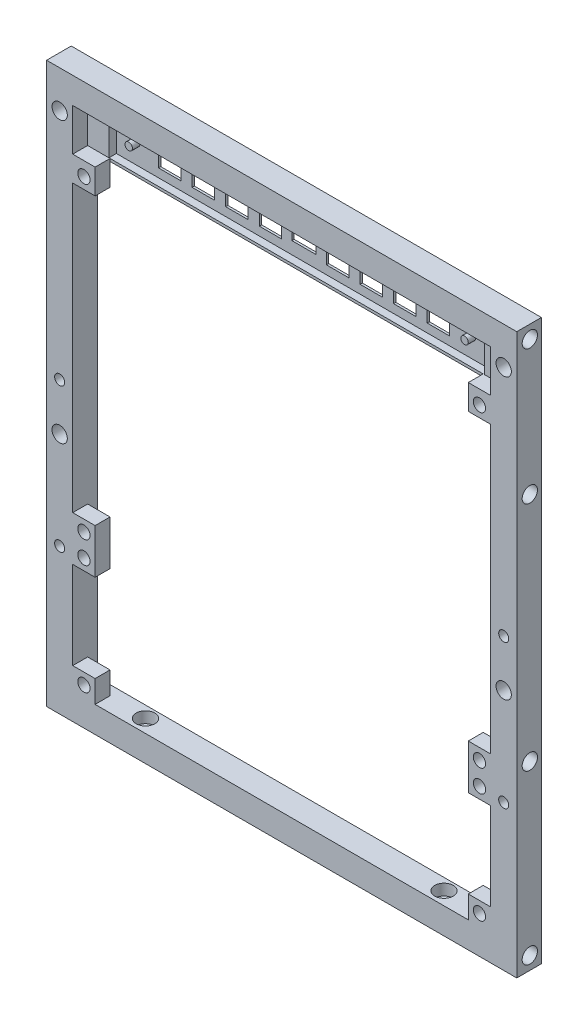
SolidWorks part; units mm, degrees
ref_plane "Front Plane" through (0, 0, 0) normal (0, 0, 1) x (1, 0, 0)
ref_plane "Top Plane" through (0, 0, 0) normal (0, 1, 0) x (1, 0, 0)
ref_plane "Right Plane" through (0, 0, 0) normal (1, 0, 0) x (0, 0, -1)
sketch "Sketch1" plane through (0, 0, 0) normal (0, 0, 1) x (1, 0, 0)
  line L1 (-63, -75) -> (63, -75)
  line L2 (-63, -75) -> (-63, 75)
  line L3 (-63, 75) -> (63, 75)
  line L4 (63, -75) -> (63, 75)
  line L5 (-63, -75) -> (63, 75) construction
  line L6 (-63, 75) -> (63, -75) construction
  line L7 (-56, -68) -> (56, -68)
  line L8 (-56, -68) -> (-56, 68)
  line L9 (-56, 68) -> (56, 68)
  line L10 (56, -68) -> (56, 68)
  line L11 (-56, -68) -> (56, 68) construction
  line L12 (-56, 68) -> (56, -68) construction
  point P0 (0, 0)
  point P6 (0, 0)
  dimension "D1" = 126
  dimension "D2" = 150
  dimension "D3" = 7
  dimension "D4" = 7
extrude "Boss-Extrude1" add sketch "Sketch1" along normal blind 7
sketch "Sketch2" plane through (-63, 0, 0) normal (-1, 0, 0) x (0, 0, 1)
  line L0 (3.5, 71.5) -> (3.5, -71.5) construction
  line L1 (7, 75) -> (0, 75) construction
  circle A0 centre (3.5, -71.5) radius 2.05
  circle A2 centre (3.5, 71.5) radius 2.05
  circle A3 centre (3.5, 35.5) radius 2.05
  circle A4 centre (3.5, -26.5) radius 2.05
  point P2 (3.5, 0)
  point P7 (3.5, 75)
  dimension "D2" = 4.1
  dimension "D3" = 36
  dimension "D4" = 45
  dimension "D1" = 3.5
extrude "Cut-Extrude1" cut sketch "Sketch2" against normal blind 6
mirror "Mirror1" about plane through (0, 0, 0) normal (1, 0, 0) of "Cut-Extrude1"
sketch "Sketch3" plane through (0, -68, 0) normal (0, 1, 0) x (1, 0, 0)
  line L0 (0, 0) -> (0, -7) construction
  line L1 (-56, 0) -> (56, 0) construction
  line L2 (-56, -7) -> (56, -7) construction
  line L3 (40, -3.5) -> (-40, -3.5) construction
  circle A0 centre (40, -3.5) radius 1.35
  circle A1 centre (-40, -3.5) radius 1.35
  point P9 (0, -3.5)
  dimension "D1" = 2.7
  dimension "D2" = 80
extrude "Cut-Extrude2" cut sketch "Sketch3" against normal through all
sketch "Sketch4" plane through (0, -68, 0) normal (0, 1, 0) x (1, 0, 0)
  circle A0 centre (40, -3.5) radius 2.5
  circle A1 centre (-40, -3.5) radius 2.5
  dimension "D1" = 5
extrude "Cut-Extrude3" cut sketch "Sketch4" against normal blind 3
sketch "Sketch5" plane through (0, 0, 0) normal (0, 0, -1) x (-1, 0, 0)
  line L0 (-59.5, -75) -> (-59.5, 75) construction
  line L1 (63, -75) -> (-63, -75) construction
  line L2 (-63, 75) -> (63, 75) construction
  line L3 (-56, 0) -> (-63, 0) construction
  line L4 (-56, -68) -> (-56, 68) construction
  line L5 (-63, -75) -> (-63, 75) construction
  line L6 (0, 75) -> (0, -75) construction
  line L7 (56, -68) -> (-56, -68) construction
  circle A0 centre (-59.5, 2.6) radius 1.35
  circle A1 centre (59.5, 2.6) radius 1.35
  circle A2 centre (-59.5, -36) radius 1.35
  circle A3 centre (59.5, -36) radius 1.35
  point P12 (-59.5, 0)
  point P13 (-59.5, 0)
  dimension "D1" = 2.7
  dimension "D2" = 2.6
  dimension "D3" = 32
extrude "Cut-Extrude4" cut sketch "Sketch5" against normal through all
sketch "Sketch6" plane through (0, 0, 0) normal (0, 0, -1) x (-1, 0, 0)
  circle A0 centre (-59.5, 2.6) radius 2.5
  circle A1 centre (59.5, 2.6) radius 2.5
  circle A2 centre (-59.5, -36) radius 2.5
  circle A3 centre (59.5, -36) radius 2.5
  dimension "D1" = 5
extrude "Cut-Extrude5" cut sketch "Sketch6" against normal blind 3
sketch "Sketch7" plane through (0, 0, 0) normal (0, 0, -1) x (-1, 0, 0)
  line L0 (-56, 68) -> (-63, 68) construction
  line L1 (-63, -75) -> (-63, 75) construction
  line L2 (-59.5, 65) -> (-59.5, -10) construction
  line L3 (-63, 75) -> (63, 75) construction
  circle A0 centre (-59.5, 65) radius 2.05
  circle A1 centre (-59.5, -10) radius 2.05
  point P8 (-59.5, 68)
  dimension "D1" = 4.1
  dimension "D2" = 10
  dimension "D3" = 75
extrude "Cut-Extrude6" cut sketch "Sketch7" against normal through all
mirror "Mirror2" about plane through (0, 0, 0) normal (1, 0, 0) of "Cut-Extrude6"
sketch "Sketch8" plane through (0, 0, 3) normal (0, 0, -1) x (-1, 0, 0)
  line L2 (-60.85, 0.4958) -> (-60.85, 4.7042)
  line L4 (-58.15, 0.4958) -> (-58.15, 4.7042)
  line L5 (-60.85, 0.4958) -> (-58.15, 4.7042) construction
  line L6 (-60.85, 4.7042) -> (-58.15, 0.4958) construction
  line L8 (-60.85, -38.1042) -> (-60.85, -33.8958)
  line L10 (-58.15, -38.1042) -> (-58.15, -33.8958)
  line L11 (-60.85, -38.1042) -> (-58.15, -33.8958) construction
  line L12 (-60.85, -33.8958) -> (-58.15, -38.1042) construction
  circle A0 centre (-59.5, 2.6) radius 2.5 construction
  circle A1 centre (-59.5, -36) radius 2.5 construction
  circle A2 centre (-59.5, -36) radius 2.5 construction
  arc A3 (-58.15, 4.7042) -> (-60.85, 4.7042) centre (-59.5, 2.6) ccw
  arc A4 (-58.15, -33.8958) -> (-60.85, -33.8958) centre (-59.5, -36) ccw
  circle A5 centre (-59.5, 2.6) radius 1.35 construction
  circle A6 centre (-59.5, -36) radius 1.35 construction
  arc A7 (-60.85, -38.1042) -> (-58.15, -38.1042) centre (-59.5, -36) ccw
  arc A8 (-60.85, 0.4958) -> (-58.15, 0.4958) centre (-59.5, 2.6) ccw
  point P0 (-59.5, 2.6)
  point P8 (-59.5, -36)
extrude "Cut-Extrude7" cut sketch "Sketch8" against normal blind 0.2
sketch "Sketch9" plane through (0, 0, 3.2) normal (0, 0, -1) x (-1, 0, 0)
  line L0 (-58.15, 2.6) -> (-58.15, 4.7042) construction
  line L1 (-60.85, 1.25) -> (-58.15, 1.25)
  line L2 (-60.85, 1.25) -> (-60.85, 3.95)
  line L3 (-60.85, 3.95) -> (-58.15, 3.95)
  line L4 (-58.15, 1.25) -> (-58.15, 3.95)
  line L5 (-60.85, 1.25) -> (-58.15, 3.95) construction
  line L6 (-60.85, 3.95) -> (-58.15, 1.25) construction
  line L7 (-58.15, -38.1042) -> (-58.15, -33.8958) construction
  line L8 (-60.85, -37.35) -> (-58.15, -37.35)
  line L9 (-60.85, -37.35) -> (-60.85, -34.65)
  line L10 (-60.85, -34.65) -> (-58.15, -34.65)
  line L11 (-58.15, -37.35) -> (-58.15, -34.65)
  line L12 (-60.85, -37.35) -> (-58.15, -34.65) construction
  line L13 (-60.85, -34.65) -> (-58.15, -37.35) construction
  arc A0 (-58.15, 2.6) -> (-60.85, 2.6) centre (-59.5, 2.6) ccw construction
  point P0 (-59.5, 2.6)
  point P8 (-59.5, -36)
extrude "Cut-Extrude8" cut sketch "Sketch9" against normal blind 0.2
mirror "Mirror3" about plane through (0, 0, 0) normal (1, 0, 0) of "Cut-Extrude8", "Cut-Extrude7"
sketch "Sketch10" plane through (0, 0, 7) normal (0, 0, 1) x (1, 0, 0)
  line L0 (56, -68) -> (56, 68) construction
  line L1 (56, -68) -> (50, -68)
  line L2 (56, -68) -> (56, -62)
  line L3 (56, -62) -> (50, -62)
  line L4 (50, -68) -> (50, -62)
  line L5 (56, -38.5) -> (50, -38.5)
  line L6 (56, -38.5) -> (56, -32.5)
  line L7 (56, -32.5) -> (50, -32.5)
  line L8 (50, -38.5) -> (50, -32.5)
  line L9 (-56, -68) -> (56, -68) construction
  dimension "D1" = 6
  dimension "D2" = 35.5
extrude "Boss-Extrude2" add sketch "Sketch10" against normal offset from surface (4 mm away) 3 up to face at (-57.45, -10, 0)
sketch "Sketch11" plane through (0, 0, 3) normal (0, 0, -1) x (-1, 0, 0)
  line L0 (-56, -38.5) -> (-50, -32.5) construction
  line L2 (-56, -68) -> (-50, -62) construction
  circle A0 centre (-53, -35.5) radius 1.65
  circle A1 centre (-53, -65) radius 1.65
  dimension "D1" = 3.3
extrude "Cut-Extrude9" cut sketch "Sketch11" against normal through all
mirror "Mirror4" about plane through (0, 0, 0) normal (1, 0, 0) of "Cut-Extrude9", "Boss-Extrude2"
sketch "Sketch12" plane through (0, 0, 0) normal (0, 0, -1) x (-1, 0, 0)
  line L0 (56, 68) -> (56, -68) construction
  line L1 (-56, 68) -> (56, 68)
  line L2 (-56, 68) -> (-56, 56)
  line L3 (-56, 56) -> (56, 56)
  line L4 (56, 68) -> (56, 56)
  dimension "D1" = 12
extrude "Boss-Extrude3" add sketch "Sketch12" against normal blind 1
sketch "Sketch13" plane through (0, 0, 1) normal (0, 0, 1) x (1, 0, 0)
  line L0 (-56, 68) -> (56, 56) construction
  line L2 (-50.3, 56.7) -> (50.3, 56.7)
  line L3 (-50.3, 56.7) -> (-50.3, 67.3)
  line L4 (-50.3, 67.3) -> (50.3, 67.3)
  line L5 (50.3, 56.7) -> (50.3, 67.3)
  line L6 (-50.3, 56.7) -> (50.3, 67.3) construction
  line L7 (-50.3, 67.3) -> (50.3, 56.7) construction
  line L8 (-56, 56) -> (56, 56)
  line L9 (-56, 56) -> (-56, 68)
  line L10 (-56, 68) -> (56, 68)
  line L11 (56, 56) -> (56, 68)
  line L12 (-56, 56) -> (56, 68) construction
  line L13 (-56, 68) -> (56, 56) construction
  point P4 (0, 62)
  point P9 (0, 62)
  dimension "D1" = 100.6
  dimension "D2" = 10.6
extrude "Boss-Extrude4" add sketch "Sketch13" along normal blind 2
sketch "Sketch14" plane through (0, 0, 1) normal (0, 0, 1) x (1, 0, 0)
  line L0 (0, 67.3) -> (0, 56.7) construction
  line L1 (50.3, 67.3) -> (-50.3, 67.3) construction
  line L2 (-50.3, 56.7) -> (50.3, 56.7) construction
  line L3 (-50.3, 62) -> (50.3, 62) construction
  line L4 (50.3, 56.7) -> (50.3, 67.3) construction
  line L5 (-33, 65) -> (-39, 65)
  line L6 (-3.25, 60) -> (3.25, 60)
  line L7 (-3.25, 60) -> (-3.25, 64)
  line L8 (-3.25, 64) -> (3.25, 64)
  line L9 (3.25, 60) -> (3.25, 64)
  line L10 (-3.25, 60) -> (3.25, 64) construction
  line L11 (-3.25, 64) -> (3.25, 60) construction
  line L12 (6, 59) -> (12, 59)
  line L13 (6, 59) -> (6, 65)
  line L14 (6, 65) -> (12, 65)
  line L15 (12, 59) -> (12, 65)
  line L16 (6, 59) -> (12, 65) construction
  line L17 (6, 65) -> (12, 59) construction
  line L18 (15, 59) -> (21, 59)
  line L19 (15, 59) -> (15, 65)
  line L20 (15, 65) -> (21, 65)
  line L21 (21, 59) -> (21, 65)
  line L22 (15, 59) -> (21, 65) construction
  line L23 (15, 65) -> (21, 59) construction
  line L24 (24, 59) -> (30, 59)
  line L25 (24, 59) -> (24, 65)
  line L26 (24, 65) -> (30, 65)
  line L27 (30, 59) -> (30, 65)
  line L28 (24, 59) -> (30, 65) construction
  line L29 (24, 65) -> (30, 59) construction
  line L30 (33, 59) -> (39, 59)
  line L31 (33, 59) -> (33, 65)
  line L32 (33, 65) -> (39, 65)
  line L33 (39, 59) -> (39, 65)
  line L34 (33, 59) -> (39, 65) construction
  line L35 (33, 65) -> (39, 59) construction
  line L36 (-39, 59) -> (-39, 65)
  line L37 (-33, 59) -> (-39, 59)
  line L38 (-33, 59) -> (-33, 65)
  line L39 (-24, 65) -> (-30, 65)
  line L40 (-30, 59) -> (-30, 65)
  line L41 (-24, 59) -> (-30, 59)
  line L42 (-24, 59) -> (-24, 65)
  line L43 (-15, 65) -> (-21, 65)
  line L44 (-21, 59) -> (-21, 65)
  line L45 (-15, 59) -> (-21, 59)
  line L46 (-15, 59) -> (-15, 65)
  line L47 (-6, 65) -> (-12, 65)
  line L48 (-12, 59) -> (-12, 65)
  line L49 (-6, 59) -> (-12, 59)
  line L50 (-6, 59) -> (-6, 65)
  circle A0 centre (-45, 62) radius 1.3 construction
  circle A1 centre (45, 62) radius 1.3 construction
  point P6 (0, 62)
  point P11 (0, 62)
  point P16 (9, 62)
  point P21 (18, 62)
  point P26 (27, 62)
  point P31 (36, 62)
  dimension "D10" = 2.6
  dimension "D9" = 45
  dimension "D1" = 6.5
  dimension "D2" = 4
  dimension "D3" = 6
  dimension "D4" = 9
  dimension "D5" = 9
  dimension "D6" = 9
  dimension "D7" = 9
  dimension "D8" = 45
extrude "Cut-Extrude10" cut sketch "Sketch14" against normal through all
sketch "Sketch15" plane through (0, 0, 1) normal (0, 0, 1) x (1, 0, 0)
  circle A0 centre (-45, 62) radius 1
  circle A1 centre (45, 62) radius 1
  dimension "D1" = 2
extrude "Boss-Extrude5" add sketch "Sketch15" along normal up to surface (2 mm away) up to face at (0, 62, 3)
chamfer "Chamfer1" distance 0.4 angle 45 4 edges at (-56, -6, 0) (56, -6, 0) (0, -68, 0) (0, 56, 0)
chamfer "Chamfer2" distance 0.4 angle 45 4 edges at (0, 75, 0) (-63, 0, 0) (0, -75, 0) (63, 0, 0)
chamfer "Chamfer3" distance 0.4 angle 45 36 edges at (-36, 59, 0) (-39, 62, 0) (-36, 65, 0) (-33, 62, 0) (-27, 59, 0) (-30, 62, 0) (-27, 65, 0) (-24, 62, 0) (-18, 59, 0) (-21, 62, 0) (-18, 65, 0) (-15, 62, 0) (-9, 59, 0) (-12, 62, 0) (-9, 65, 0) (-6, 62, 0) (0, 60, 0) (-3.25, 62, 0) (0, 64, 0) (3.25, 62, 0) (9, 59, 0) (6, 62, 0) (9, 65, 0) (12, 62, 0) (18, 59, 0) (15, 62, 0) (18, 65, 0) (21, 62, 0) (36, 59, 0) (33, 62, 0) (36, 65, 0) (39, 62, 0) (27, 59, 0) (24, 62, 0) (27, 65, 0) (30, 62, 0)
sketch "Sketch16" plane through (0, 0, 7) normal (0, 0, 1) x (1, 0, 0)
  line L0 (-50, 56) -> (-50, 56.7)
  line L1 (-56, -32.5) -> (-50, -32.5)
  line L2 (-56, -32.5) -> (-56, -26.5)
  line L3 (-56, -26.5) -> (-50, -26.5)
  line L4 (-50, -32.5) -> (-50, -26.5)
  line L5 (56, -32.5) -> (50, -32.5)
  line L6 (56, -32.5) -> (56, -26.5)
  line L7 (56, -26.5) -> (50, -26.5)
  line L8 (50, -32.5) -> (50, -26.5)
  line L9 (56, 56) -> (50, 56) construction
  line L10 (56, 56) -> (56, 50)
  line L11 (56, 50) -> (50, 50)
  line L12 (50, 56) -> (50, 50)
  line L13 (-56, 56) -> (-50, 56) construction
  line L14 (-56, 56) -> (-56, 50)
  line L15 (-56, 50) -> (-50, 50)
  line L16 (-50, 56) -> (-50, 50)
  line L17 (-50.3, 56.7) -> (50.3, 56.7) construction
  line L18 (-50, 56.7) -> (-56, 56.7)
  line L19 (-56, 68) -> (-56, 56) construction
  line L20 (-56, 56.7) -> (-56, 56)
  line L21 (50, 56) -> (50, 56.7)
  line L22 (50, 56.7) -> (56, 56.7)
  line L23 (56, 56) -> (56, 68) construction
  line L24 (56, 56.7) -> (56, 56)
  dimension "D1" = 6
extrude "Boss-Extrude7" add sketch "Sketch16" against normal offset from surface (4 mm away) 3 up to face at (-36, 62, 0)
sketch "Sketch17" plane through (0, 0, 3) normal (0, 0, -1) x (-1, 0, 0)
  line L0 (-50, 50) -> (50, -26.5) construction
  line L1 (-50, -26.5) -> (-50, -38.5) construction
  line L2 (-53, -29.5) -> (53, -29.5) construction
  line L3 (-53, -29.5) -> (-53, 53) construction
  line L4 (-53, 53) -> (53, 53) construction
  line L5 (53, -29.5) -> (53, 53) construction
  line L6 (-53, -29.5) -> (53, 53) construction
  line L7 (-53, 53) -> (53, -29.5) construction
  line L8 (50, -26.5) -> (56, -26.5) construction
  circle A0 centre (-53, -29.5) radius 1.65
  circle A1 centre (53, -29.5) radius 1.65
  circle A2 centre (53, 53) radius 1.65
  circle A3 centre (-53, 53) radius 1.65
  point P4 (0, 11.75)
  dimension "D3" = 3.3
  dimension "D1" = 3
  dimension "D2" = 3
extrude "Cut-Extrude11" cut sketch "Sketch17" against normal through all
